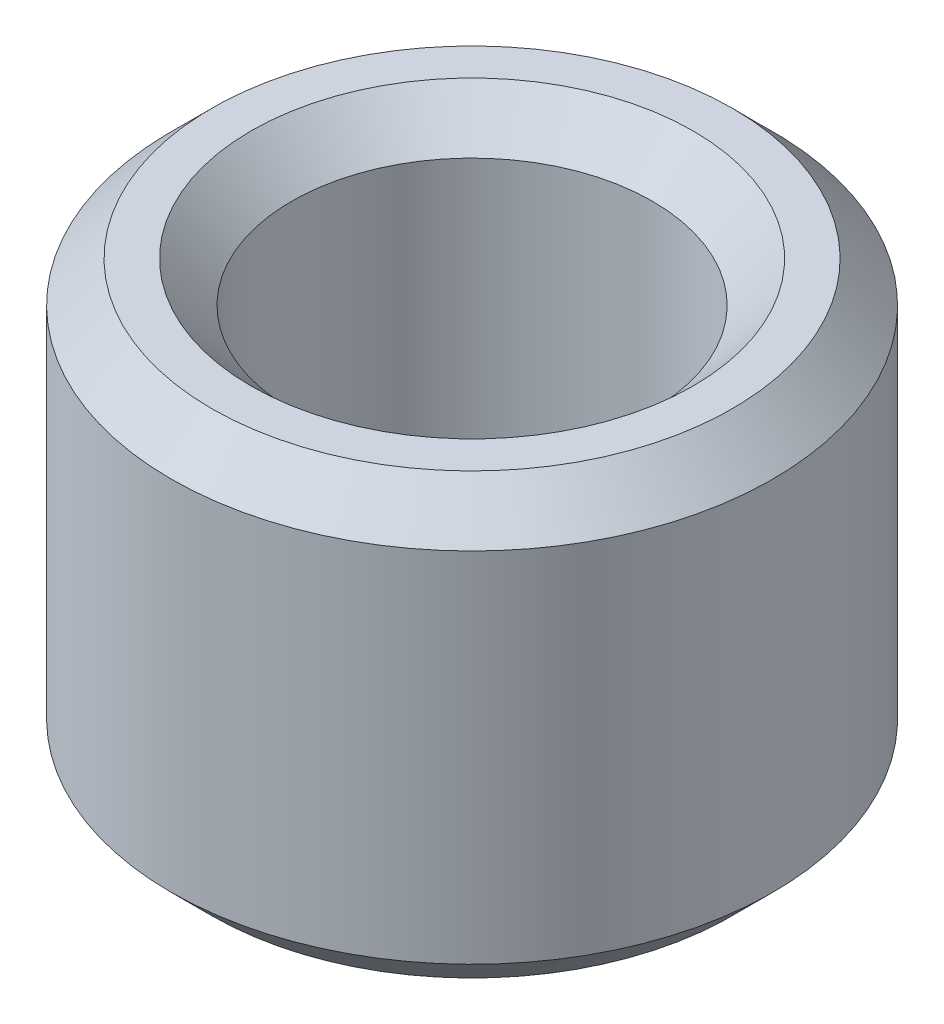
SolidWorks part; units mm, degrees
ref_plane "Front Plane" through (0, 0, 0) normal (0, 0, 1) x (1, 0, 0)
ref_plane "Top Plane" through (0, 0, 0) normal (0, 1, 0) x (1, 0, 0)
ref_plane "Right Plane" through (0, 0, 0) normal (1, 0, 0) x (0, 0, -1)
sketch "Sketch1" plane through (0, 0, 0) normal (0, 1, 0) x (1, 0, 0)
  circle A0 centre (0, 0) radius 12.5
  dimension "SLEEVE_OD" = 25
extrude "Boss-Extrude1" add sketch "Sketch1" along normal blind 18.2442
sketch "Sketch2" plane through (0, 0, 0) normal (0, 1, 0) x (1, 0, 0)
  circle A0 centre (0, 0) radius 7.4949
  dimension "BORE_D" = 14.9899
extrude "Cut-Extrude1" cut sketch "Sketch2" along normal through all
chamfer "Chamfer1" distance 1.6874 angle 45 4 edges at (0, 18.2442, 7.4949) (0, 0, 7.4949) (0, 0, 12.5) (0, 18.2442, 12.5)
